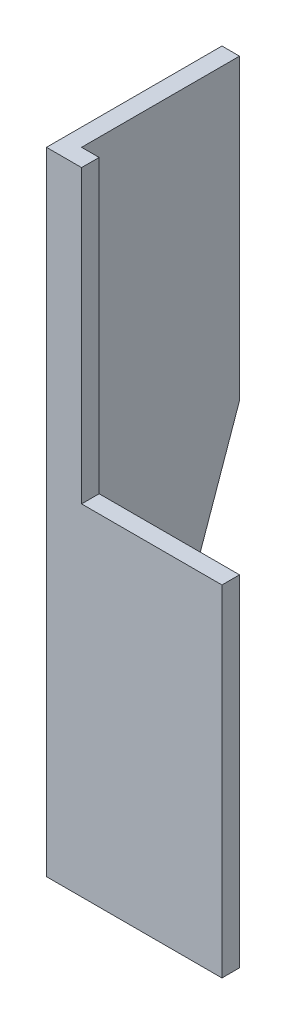
SolidWorks part; units mm, degrees
ref_plane "Alzado" through (0, 0, 0) normal (0, 0, 1) x (1, 0, 0)
ref_plane "Planta" through (0, 0, 0) normal (0, 1, 0) x (1, 0, 0)
ref_plane "Vista lateral" through (0, 0, 0) normal (1, 0, 0) x (0, 0, -1)
sketch "Croquis1" plane through (0, 0, 0) normal (0, 1, 0) x (1, 0, 0)
  line L0 (0, 0) -> (0, 50)
  line L1 (0, 0) -> (50, 0)
  line L2 (5, 5) -> (50, 5)
  line L3 (5, 5) -> (5, 50)
  line L4 (0, 50) -> (5, 50)
  line L5 (50, 5) -> (50, 0)
  dimension "D1" = 50
  dimension "D2" = 5
extrude "Saliente-Extruir1" add sketch "Croquis1" along normal blind 180
sketch "Croquis2" plane through (0, 0, 0) normal (-1, 0, 0) x (0, 0, 1)
  line L0 (-50, 95) -> (0, 95) construction
  line L1 (-50, 180) -> (-50, 0) construction
  line L2 (0, 180) -> (0, 0) construction
  line L3 (-50, 180) -> (0, 180) construction
  line L4 (-50, 95) -> (-16.6667, 0)
  line L5 (-50, 0) -> (0, 0) construction
  line L6 (-16.6667, 0) -> (0, 0)
  line L9 (-50, 95) -> (-50, 0)
  line L10 (-50, 0) -> (-16.6667, 0)
  line M8 (-50, 0) -> (0, 0)
  line M11 (-50, 180) -> (-50, 0)
  dimension "D1" = 85
  dimension "D2" = 16.6667
extrude "Cortar-Extruir1" cut sketch "Croquis2" against normal up to surface (5 mm away) contours L4 M11 M8 region at (0, 31.6667, -38.8889) up to face at (5, 90, -27.5)
sketch "Croquis3" plane through (0, 0, 0) normal (0, 0, 1) x (1, 0, 0)
  line L0 (0, 180) -> (0, 0) construction
  line L1 (50, 180) -> (10, 180)
  line L2 (50, 180) -> (50, 97)
  line L3 (50, 97) -> (10, 97)
  line L4 (10, 180) -> (10, 97)
  dimension "D1" = 10
  dimension "D2" = 83
extrude "Cortar-Extruir2" cut sketch "Croquis3" against normal up to surface (5 mm away) up to face at (27.5, 90, -5)
